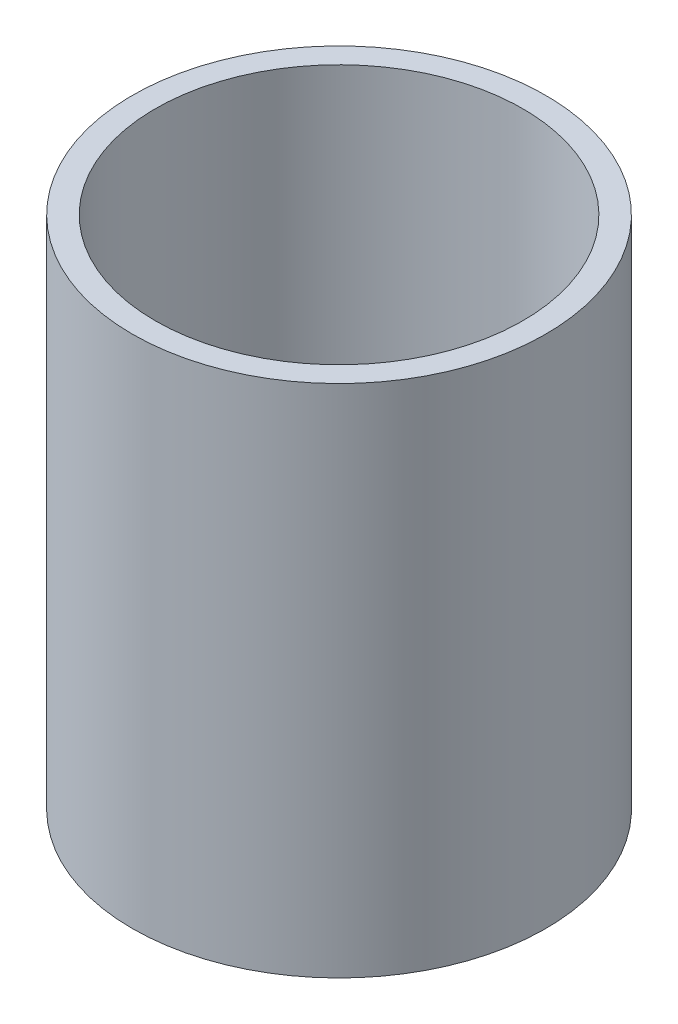
SolidWorks part; units mm, degrees
ref_plane "Front Plane" through (0, 0, 0) normal (0, 0, 1) x (1, 0, 0)
ref_plane "Top Plane" through (0, 0, 0) normal (0, 1, 0) x (1, 0, 0)
ref_plane "Right Plane" through (0, 0, 0) normal (1, 0, 0) x (0, 0, -1)
sketch "Sketch1" plane through (0, 0, 0) normal (0, 1, 0) x (1, 0, 0)
  circle A0 centre (0, 0) radius 32.5
  dimension "SLEEVE_OD" = 65
extrude "Boss-Extrude1" add sketch "Sketch1" along normal blind 80.9207
sketch "Sketch2" plane through (0, 0, 0) normal (0, 1, 0) x (1, 0, 0)
  circle A0 centre (0, 0) radius 28.8839
  dimension "BORE_D" = 57.7677
extrude "Cut-Extrude1" cut sketch "Sketch2" along normal through all
chamfer "Chamfer1" distance 1.6459 angle 60.523 rebuild error yes
